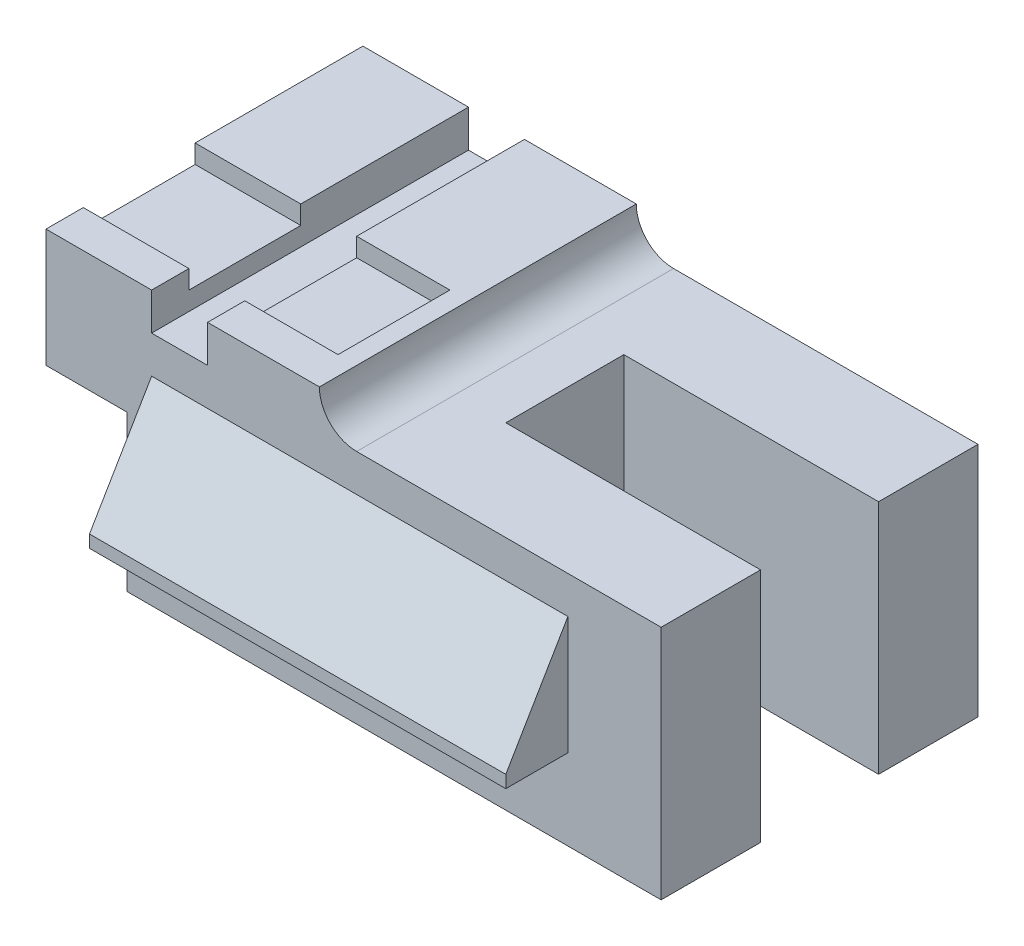
SolidWorks part; units mm, degrees
ref_plane "Piano frontale" through (0, 0, 0) normal (0, 0, 1) x (1, 0, 0)
ref_plane "Piano superiore" through (0, 0, 0) normal (0, 1, 0) x (1, 0, 0)
ref_plane "Piano destro" through (0, 0, 0) normal (1, 0, 0) x (0, 0, -1)
sketch "Schizzo1" plane through (0, 0, 0) normal (0, 1, 0) x (1, 0, 0)
  line L1 (0, 0) -> (-99, 0)
  line L2 (0, 0) -> (0, 51)
  line L3 (0, 51) -> (-99, 51)
  line L4 (-99, 0) -> (-99, 51)
  dimension "D1" = 99
  dimension "D2" = 51
extrude "Estrusione-Estrusione1" add sketch "Schizzo1" along normal blind 44
sketch "Schizzo2" plane through (0, 44, 0) normal (0, 1, 0) x (1, 0, 0)
  line L0 (-99, 0) -> (0, 0) construction
  line L1 (0, 51) -> (-55, 51)
  line L2 (0, 51) -> (0, 0)
  line L3 (0, 0) -> (-55, 0)
  line L4 (-55, 51) -> (-55, 0)
  dimension "D1" = 55
extrude "Taglio-Estrusione1" cut sketch "Schizzo2" against normal blind 6
sketch "Schizzo3" plane through (0, 44, 0) normal (0, 1, 0) x (1, 0, 0)
  line L0 (-99, 51) -> (-99, 0) construction
  line L1 (-99, 24) -> (-58, 24)
  line L2 (-99, 24) -> (-99, 6)
  line L3 (-99, 6) -> (-58, 6)
  line L4 (-58, 24) -> (-58, 6)
  line L5 (-55, 51) -> (-99, 51) construction
  dimension "D1" = 41
  dimension "D2" = 27
  dimension "D3" = 18
extrude "Taglio-Estrusione2" cut sketch "Schizzo3" against normal blind 3
sketch "Schizzo4" plane through (0, 44, 0) normal (0, 1, 0) x (1, 0, 0)
  line L0 (-55, 51) -> (-99, 51) construction
  line L1 (-82, 51) -> (-73, 51)
  line L2 (-82, 51) -> (-82, 0)
  line L3 (-82, 0) -> (-73, 0)
  line L4 (-73, 51) -> (-73, 0)
  line L5 (-99, 0) -> (-55, 0) construction
  line L6 (-99, 51) -> (-99, 24) construction
  dimension "D1" = 9
  dimension "D2" = 17
extrude "Taglio-Estrusione3" cut sketch "Schizzo4" against normal blind 6
sketch "Schizzo5" plane through (0, 38, 0) normal (0, 1, 0) x (1, 0, 0)
  line L0 (0, 0) -> (0, 51) construction
  line L1 (0, 35) -> (-41, 35)
  line L2 (0, 35) -> (0, 16)
  line L3 (0, 16) -> (-41, 16)
  line L4 (-41, 35) -> (-41, 16)
  line L5 (-55, 0) -> (0, 0) construction
  dimension "D1" = 41
  dimension "D2" = 19
  dimension "D3" = 16
extrude "Taglio-Estrusione4" cut sketch "Schizzo5" against normal through all
sketch "Schizzo6" plane through (0, 0, 0) normal (0, 0, 1) x (1, 0, 0)
  line L1 (-99, 0) -> (-86, 0)
  line L2 (-99, 0) -> (-99, 25)
  line L3 (-99, 25) -> (-86, 25)
  line L4 (-86, 0) -> (-86, 25)
  dimension "D1" = 13
  dimension "D2" = 25
extrude "Taglio-Estrusione5" cut sketch "Schizzo6" against normal through all
sketch "Schizzo7" plane through (0, 0, 0) normal (0, 0, 1) x (1, 0, 0)
  line L0 (-86, 0) -> (0, 0) construction
  line L1 (-82, 32) -> (-15, 32)
  line L2 (-82, 32) -> (-82, 13)
  line L3 (-82, 13) -> (-15, 13)
  line L4 (-15, 32) -> (-15, 13)
  line L5 (0, 38) -> (0, 0) construction
  dimension "D1" = 67
  dimension "D2" = 19
  dimension "D3" = 13
  dimension "D4" = 15
extrude "Estrusione-Estrusione2" add sketch "Schizzo7" along normal blind 10
sketch "Schizzo8" plane through (-15, 0, 0) normal (1, 0, 0) x (0, 0, -1)
  line L0 (0, 32) -> (-10, 15)
  line L1 (-10, 32) -> (0, 32) construction
  line L2 (-10, 13) -> (-10, 32) construction
  line L3 (-10, 15) -> (-10, 32)
  line L4 (-10, 32) -> (0, 32)
  line L5 (-10, 13) -> (0, 13) construction
  point P8 (0, 0)
  dimension "D1" = 2
extrude "Taglio-Estrusione6" cut sketch "Schizzo8" against normal through all
fillet "Raccordo1" radius 6 1 edges at (-55, 38, -25.5)
